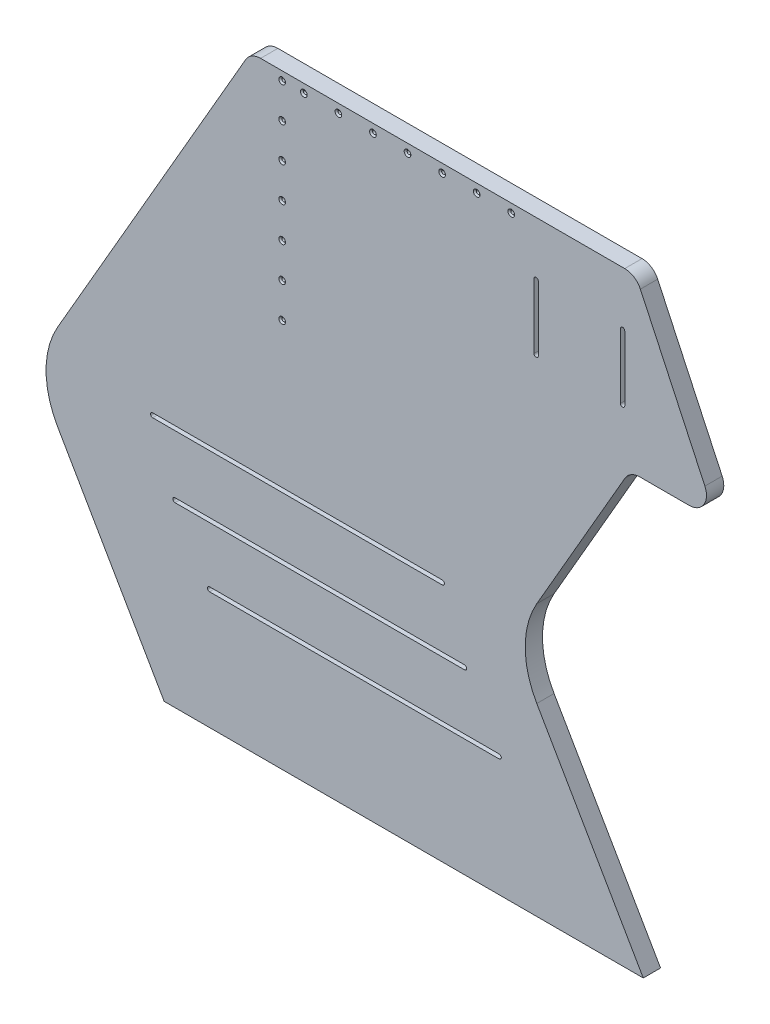
SolidWorks part; units mm, degrees
ref_plane "Front Plane" through (0, 0, 0) normal (0, 0, 1) x (1, 0, 0)
ref_plane "Top Plane" through (0, 0, 0) normal (0, 1, 0) x (1, 0, 0)
ref_plane "Right Plane" through (0, 0, 0) normal (1, 0, 0) x (0, 0, -1)
sketch "Sketch1" plane through (0, 0, 0) normal (0, 0, 1) x (1, 0, 0)
  line L12 (0, 0) -> (-193.1322, 334.5148)
  line L13 (-193.1322, 334.5148) -> (-19.647, 635)
  line L15 (107.353, 635) -> (-11.0891, 889)
  line L16 (-11.0891, 889) -> (-576.9054, 889)
  line L19 (-703.9054, 0) -> (0, 0)
  line L20 (-703.9054, 0) -> (-897.0376, 334.5148)
  line L21 (-897.0376, 334.5148) -> (-576.9054, 889)
  line L22 (-527.9291, -304.8) -> (-897.0376, 334.5148) construction
  line L23 (-193.1322, 334.5148) -> (-48.9764, 584.2) construction
  line L24 (-19.647, 635) -> (107.353, 635)
  line L25 (-897.0376, 334.5148) -> (-193.1322, 334.5148) construction
  dimension "D1" = 609.6
  dimension "D2" = 60
  dimension "D3" = 889
  dimension "D4" = 127
  dimension "D6" = 127
  dimension "D7" = 254
  dimension "D8" = 65
extrude "Boss-Extrude1" add sketch "Sketch1" along normal blind 25.4
fillet "Fillet1" radius 127 2 edges at (-193.1322, 334.5148, 12.7) (-897.0376, 334.5148, 12.7)
fillet "Fillet2" radius 25.4 4 edges at (107.353, 635, 12.7) (-576.9054, 889, 12.7) (-11.0891, 889, 12.7) (-19.647, 635, 12.7)
hole_wizard "wheel slot" positions "Sketch2" profile "Sketch3" size "1/4" standard "ANSI Inch" slot yes end condition through all
sketch "Sketch2" plane through (0, 0, 25.4) normal (0, 0, 1) x (1, 0, 0)
  line L0 (-30.3823, 711.2) -> (-30.3823, 812.8) construction
  line L1 (-4.9823, 635) -> (-4.9823, 889) construction
  line L2 (-4.9823, 889) -> (-27.2707, 889) construction
  line L4 (-30.3823, 762) -> (-4.9823, 762) construction
  line L6 (-157.3823, 762) -> (-30.3823, 762) construction
  point P0 (-30.3823, 762)
  point P4 (-157.3823, 762)
  dimension "D1" = 101.6
  dimension "D2" = 127
  dimension "D3" = 25.4
sketch "Sketch3" plane through (-30.3823, 762, 25.4) normal (1, 0, 0) x (0, -1, 0)
  line L0 (0, 0) -> (0, 25.4)
  line L1 (0, 25.4) -> (3.175, 25.4)
  line L2 (3.175, 25.4) -> (3.175, 0)
  line L5 (3.175, 0) -> (0, 0)
  line L11 (0, -6.35) -> (0, 107.95) construction
  dimension "Thru Hole Dia." = 6.35
  dimension "Thru Hole Depth" = 25.4
hole_wizard "pedal slot" positions "Sketch4" profile "Sketch5" size "1/4" standard "ANSI Inch" slot yes end condition through all
sketch "Sketch4" plane through (0, 0, 25.4) normal (0, 0, 1) x (1, 0, 0)
  line L0 (-640.4054, 175.9764) -> (-208.6054, 175.9764) construction
  line L6 (-475.3054, 263.9645) -> (-322.9054, 0)
  line L8 (-703.9054, 0) -> (0, 0) construction
  line L14 (-475.3054, 263.9645) -> (-508, 355.6)
  line L18 (-860.3759, 271.0148) -> (-703.9054, 0) construction
  point P0 (-424.5054, 175.9764)
  point P4 (-475.3054, 263.9645)
  point P47 (-508, 355.6)
  dimension "D1" = 431.8
  dimension "D3" = 203.2
  dimension "D4" = 101.6
  dimension "D5" = 355.6
  dimension "D2" = 381
  dimension "D6" = 508
sketch "Sketch5" plane through (-424.5054, 175.9764, 25.4) normal (1, 0, 0) x (0, -1, 0)
  line L0 (0, 0) -> (0, 25.4)
  line L1 (0, 25.4) -> (3.175, 25.4)
  line L2 (3.175, 25.4) -> (3.175, 0)
  line L5 (3.175, 0) -> (0, 0)
  line L11 (0, -6.35) -> (0, 107.95) construction
  dimension "Thru Hole Dia." = 6.35
  dimension "Thru Hole Depth" = 25.4
hole_wizard "CSK for #10 Flat Head Machine Screw (100)1" positions "Sketch6" profile "Sketch7" countersink size "#10" standard "ANSI Inch" end condition through all
sketch "Sketch6" plane through (0, 0, 25.4) normal (0, 0, 1) x (1, 0, 0)
  line L0 (-530.4908, 889) -> (-530.4908, 876.3)
  line L1 (-27.2707, 889) -> (-562.2408, 889) construction
  line L4 (-530.4908, 876.3) -> (-530.4908, 825.5)
  line L5 (-530.4908, 876.3) -> (-498.7408, 876.3)
  line L6 (-498.7408, 876.3) -> (-447.9408, 876.3)
  line L7 (-447.9408, 876.3) -> (-397.1408, 876.3)
  line L8 (-397.1408, 876.3) -> (-346.3408, 876.3)
  line L9 (-346.3408, 876.3) -> (-295.5408, 876.3)
  line L10 (-295.5408, 876.3) -> (-244.7408, 876.3)
  line L11 (-530.4908, 825.5) -> (-530.4908, 774.7)
  line L12 (-530.4908, 774.7) -> (-530.4908, 723.9)
  line L13 (-530.4908, 723.9) -> (-530.4908, 673.1)
  line L14 (-530.4908, 673.1) -> (-530.4908, 622.3)
  line L15 (-530.4908, 622.3) -> (-530.4908, 571.5)
  line L16 (-244.7408, 876.3) -> (-193.9408, 876.3)
  arc A0 (-562.2408, 889) -> (-584.2378, 876.3) centre (-562.2408, 863.6) ccw construction
  point P0 (-530.4908, 876.3)
  point P13 (-530.4908, 825.5)
  point P17 (-498.7408, 876.3)
  point P19 (-447.9408, 876.3)
  point P20 (-397.1408, 876.3)
  point P21 (-346.3408, 876.3)
  point P22 (-295.5408, 876.3)
  point P24 (-244.7408, 876.3)
  point P41 (-530.4908, 774.7)
  point P43 (-530.4908, 723.9)
  point P45 (-530.4908, 673.1)
  point P47 (-530.4908, 622.3)
  point P49 (-530.4908, 571.5)
  point P74 (-193.9408, 876.3)
  dimension "D1" = 50.8
  dimension "D2" = 31.75
  dimension "D3" = 50.8
  dimension "D4" = 12.7
  dimension "D5" = 31.75
sketch "Sketch7" plane through (-530.4908, 876.3, 25.4) normal (1, 0, 0) x (0, -1, 0)
  line L0 (0, 0) -> (0, 25.4)
  line L1 (0, 25.4) -> (2.5527, 25.4)
  line L2 (2.5527, 25.4) -> (2.5527, 1.9608)
  line L3 (2.5527, 1.9608) -> (4.8895, 0)
  line L5 (4.8895, 0) -> (0, 0)
  line L6 (-2.5527, 1.9608) -> (-4.8895, 0) construction
  line L11 (0, -6.35) -> (0, 107.95) construction
  dimension "Thru Hole Dia." = 5.1054
  dimension "Thru Hole Depth" = 25.4
  dimension "Near C'Sink Dia." = 9.779
  dimension "Near C'Sink Angle" = 100
